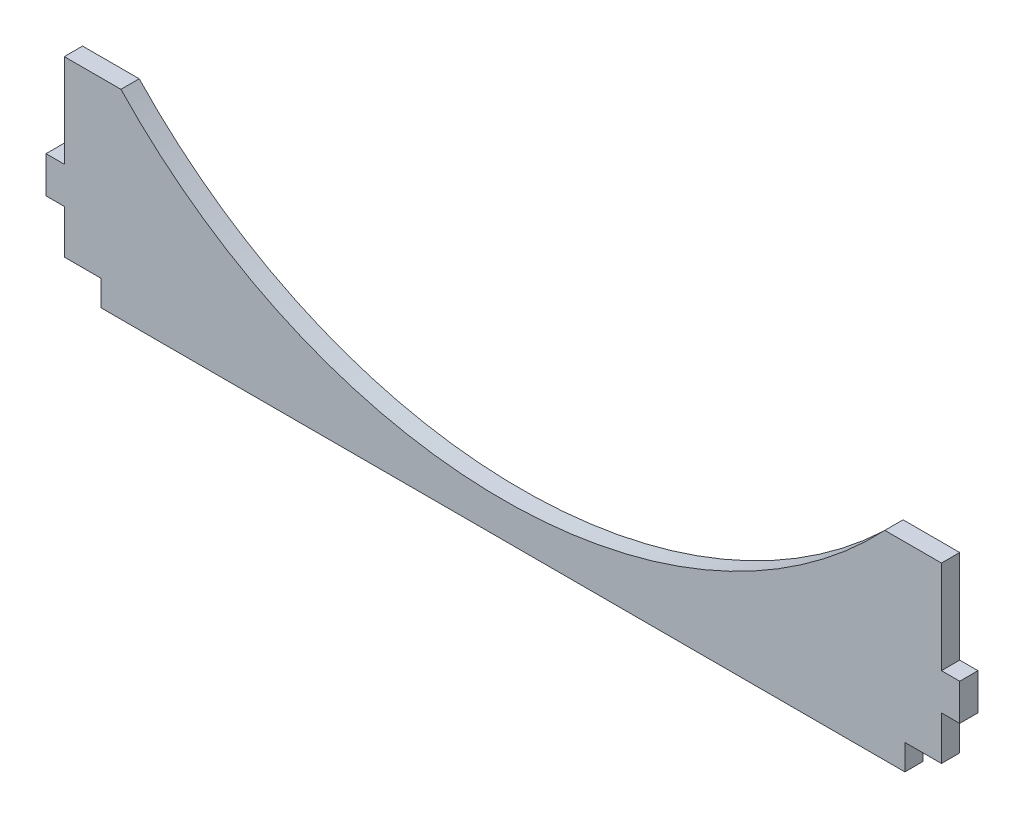
SolidWorks part; units mm, degrees
material "Papier ondulé"
ref_plane "Plan de face" through (0, 0, 0) normal (0, 0, 1) x (1, 0, 0)
ref_plane "Plan de dessus" through (0, 0, 0) normal (0, 1, 0) x (1, 0, 0)
ref_plane "Plan de droite" through (0, 0, 0) normal (1, 0, 0) x (0, 0, -1)
sketch "Esquisse1" plane through (0, 0, 0) normal (0, 0, 1) x (1, 0, 0)
  line L0 (0, 0) -> (-15.5, 0)
  line L1 (-15.5, 0) -> (-15.5, -25.5)
  line L2 (-15.5, -25.5) -> (-20.5, -25.5)
  line L3 (-20.5, -25.5) -> (-20.5, -35.5)
  line L4 (-20.5, -35.5) -> (-15.5, -35.5)
  line L5 (-15.5, -35.5) -> (-15.5, -54.5)
  line L6 (-15.5, -54.5) -> (224.5, -54.5)
  line L7 (224.5, -54.5) -> (224.5, -35.5)
  line L8 (224.5, -35.5) -> (229.5, -35.5)
  line L9 (229.5, -35.5) -> (229.5, -25.5)
  line L10 (229.5, -25.5) -> (224.5, -25.5)
  line L11 (224.5, -25.5) -> (224.5, 0)
  line L12 (224.5, 0) -> (209, 0)
  arc A0 (209, 0) -> (0, 0) centre (104.5, 98.8361) cw
  point P17 (104.5, -45)
  dimension "D1" = 15.5
  dimension "D2" = 5
  dimension "D3" = 25.5
  dimension "D4" = 10
  dimension "D5" = 19
  dimension "D6" = 240
  dimension "D7" = 9.5
extrude "Boss.-Extru.1" add sketch "Esquisse1" along normal blind 5
sketch "Esquisse2" plane through (0, 0, 5) normal (0, 0, 1) x (1, 0, 0)
  line L1 (-15.5, -54.5) -> (-5.5, -54.5)
  line L2 (-15.5, -54.5) -> (-15.5, -47.5)
  line L3 (-15.5, -47.5) -> (-5.5, -47.5)
  line L4 (-5.5, -54.5) -> (-5.5, -47.5)
  line L5 (224.5, -54.5) -> (214.5, -54.5)
  line L6 (224.5, -54.5) -> (224.5, -47.5)
  line L7 (224.5, -47.5) -> (214.5, -47.5)
  line L8 (214.5, -54.5) -> (214.5, -47.5)
  dimension "D1" = 10
  dimension "D2" = 7
extrude "Enlèv. mat.-Extru.1" cut sketch "Esquisse2" against normal through all
